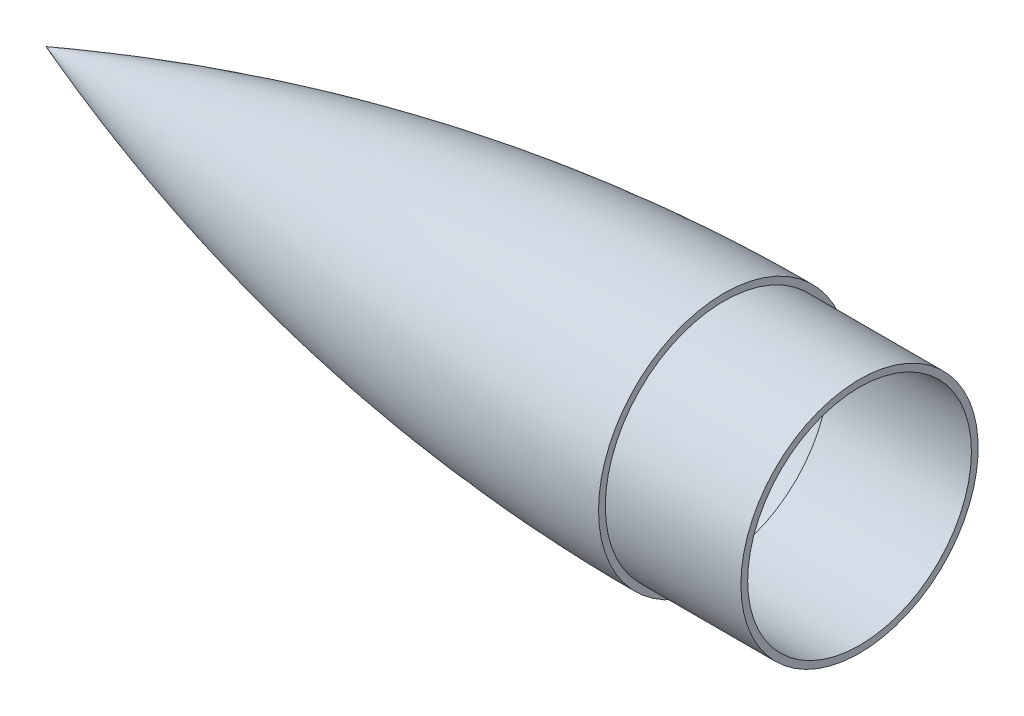
SolidWorks part; units mm, degrees
ref_plane "前基準面" through (0, 0, 0) normal (0, 0, 1) x (1, 0, 0)
ref_plane "上基準面" through (0, 0, 0) normal (0, 1, 0) x (1, 0, 0)
ref_plane "右基準面" through (0, 0, 0) normal (1, 0, 0) x (0, 0, -1)
ref_axis "基準軸1" through (88.99, 0, 0) along (-1, 0, 0)
ref_axis "基準軸2" through (0, -55, 0) along (0, 1, 0)
ref_axis "基準軸3" through (0, 0, -88.99) along (0, 0, 1)
sketch "草圖1" plane through (0, 0, 0) normal (0, 0, 1) x (1, 0, 0)
  line L0 (0, 0) -> (400, 0)
  line L3 (400, 70) -> (400, 74)
  line L4 (400, 70) -> (480, 70)
  line L5 (480, 70) -> (480, 0)
  line L6 (480, 0) -> (400, 0)
  spline S0 degree 2 poles (-38.2281, -14.8203) (200.886, 82.1072) (440, 73.26) knots 0 0 0 1 1 1 construction
  spline S1 degree 2 poles (0, 0) (200, 74) (400, 74) knots 0.079937 0.079937 0.079937 0.916358 0.916358 0.916358
  dimension "D1" = 400
  dimension "D2" = 4
  dimension "D3" = 80
revolve "旋轉1" add sketch "草圖1" angle 360 about L0
shell "薄殼1" thickness 4 removed face at (480, 0, 70)
